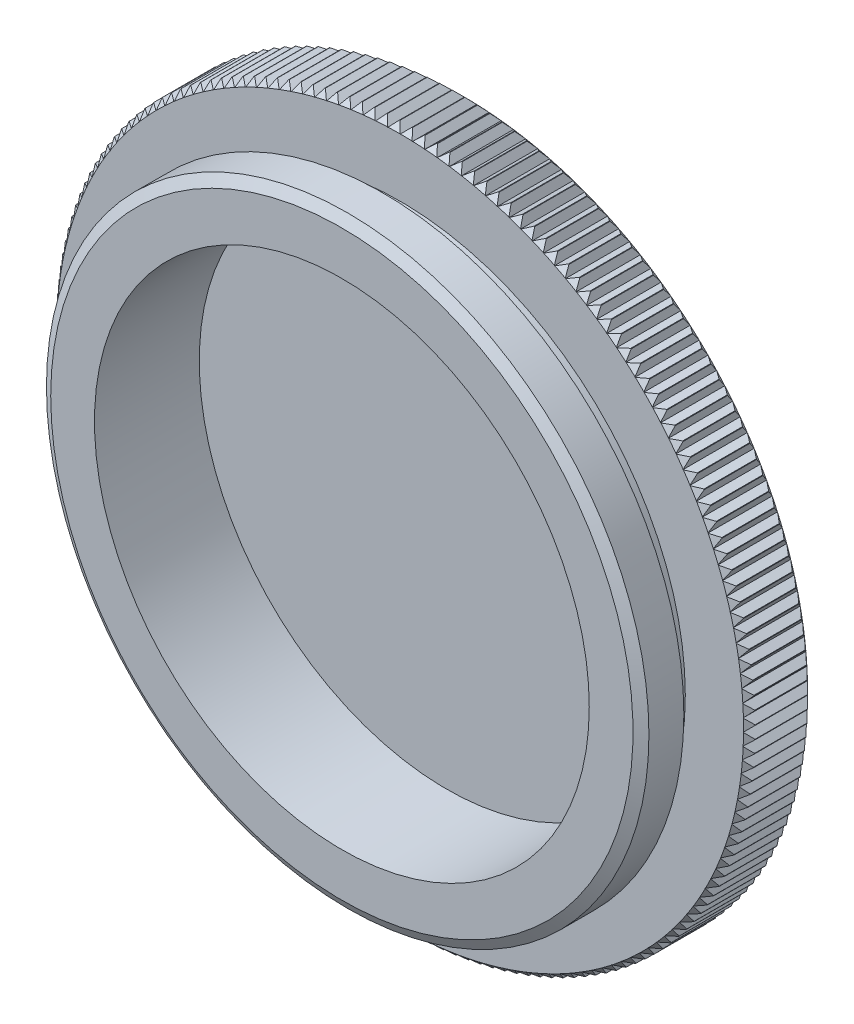
SolidWorks part; units mm, degrees
material "Anodized Aluminum"
ref_plane "Front Plane" through (0, 0, 0) normal (0, 0, 1) x (1, 0, 0)
ref_plane "Top Plane" through (0, 0, 0) normal (0, 1, 0) x (1, 0, 0)
ref_plane "Right Plane" through (0, 0, 0) normal (1, 0, 0) x (0, 0, -1)
sketch "Sketch1" plane through (0, 0, 0) normal (1, 0, 0) x (0, 0, -1)
  line L0 (0, 0) -> (1.3938, 0) construction
  line L1 (1.3938, 0) -> (1.3938, 15.24)
  line L2 (-3.9402, 0) -> (-3.9402, 13.1445)
  line L3 (1.3938, 15.24) -> (-1.4002, 15.24)
  line L4 (-1.4002, 15.24) -> (-1.4002, 12.446)
  line L5 (-1.4002, 12.446) -> (-2.1622, 12.446)
  line L6 (-2.1622, 12.446) -> (-2.1622, 13.1445)
  line L7 (-2.1622, 13.1445) -> (-3.9402, 13.1445)
  line L8 (-3.9402, 0) -> (1.3938, 0)
  dimension "D1" = 15.24
  dimension "D2" = 5.334
  dimension "D3" = 2.54
  dimension "D4" = 0.762
  dimension "D5" = 13.1445
  dimension "D6" = 12.446
revolve "Revolve1" add sketch "Sketch1" angle 360 about L0
sketch "Sketch2" plane through (0, 0, 3.9402) normal (0, 0, 1) x (1, 0, 0)
  circle A0 centre (0, 0) radius 10.795
extrude "Cut-Extrude1" cut sketch "Sketch2" against normal blind 4.572
chamfer "Chamfer1" distance 0.254 angle 60 1 edges at (13.1445, 0, 3.9402) first distance on face at (13.1445, 0, 3.9402)
chamfer "Chamfer2" distance 0.254 angle 45 2 edges at (15.24, 0, -1.3938) (15.24, 0, 1.4002)
sketch "Sketch3" plane through (0, 0, -1.3938) normal (0, 0, -1) x (-1, 0, 0)
  line L0 (0, 0) -> (0, 15.24) construction
  line L1 (0, 14.9754) -> (0.2623, 15.2377)
  line L2 (0, 14.9754) -> (-0.2623, 15.2377)
  line L3 (-0.2623, 15.2377) -> (-0.2623, 15.3523)
  line L4 (-0.2623, 15.3523) -> (0.2623, 15.3523)
  line L5 (0.2623, 15.3523) -> (0.2623, 15.2377)
  circle A0 centre (0, 0) radius 15.24 construction
  point P4 (0, 14.9754)
  dimension "D1" = 0.2646
extrude "Cut-Extrude2" cut sketch "Sketch3" against normal up to next
pattern_circular "CirPattern2" count 175 over 360 about axis through (0, 0, 0) along (0, 0, 1) of "Cut-Extrude2"
ref_plane "Plane1" through (0, 0, -1.3938) normal (0, 0, -1) x (-1, 0, 0)
sketch "Sketch6" plane through (0, 0, -1.3938) normal (0, 0, -1) x (-1, 0, 0)
  arc A0 (-11.43, 0) -> (11.43, 0) centre (0, 0) ccw construction
  text T0 "SM1CP2" font "Verdana" height 2.286
  dimension "D1" = 22.86
extrude "Cut-Extrude3" cut sketch "Sketch6" against normal blind 0.0254
sketch "Sketch7" plane through (0, 0, -1.3938) normal (0, 0, -1) x (-1, 0, 0)
  line B0 (-4.1249, 10.6598) -> (-4.5024, 11.6352)
  line B1 (-5.2654, 11.3104) -> (-4.8214, 10.3633)
  line B2 (-5.3362, 10.1079) -> (-6.2566, 11.8506)
  line B3 (-6.8728, 11.5042) -> (-5.856, 9.8159)
  line B4 (-6.342, 9.5092) -> (-7.4378, 11.1472)
  line B5 (-8.0648, 10.7024) -> (-8.4074, 11.1569)
  line B6 (-5.8997, 12.6631) -> (-5.507, 11.8256)
  line B7 (-4.7079, 12.1659) -> (-5.0417, 13.0285)
  line B8 (-4.3872, 13.2632) -> (-3.5838, 10.8536)
  line B9 (4.6468, 11.7023) -> (4.4107, 11.1076)
  line B10 (4.698, 11.5533) -> (4.5444, 11.1713)
  line B11 (4.7448, 11.9491) -> (4.9496, 12.4651)
  line B12 (5.0131, 12.3083) -> (4.8923, 12.0115)
  line B13 (3.2648, 12.8314) -> (2.7647, 12.0086)
  line B14 (3.2122, 11.3589) -> (3.2312, 10.9638)
  line B15 (2.4674, 11.1605) -> (2.679, 11.4964)
  line B16 (-0.9686, 12.317) -> (-0.8948, 11.3949)
  line B17 (-1.4664, 11.3355) -> (-1.8001, 13.8535)
  line B18 (0.0885, 12.6179) -> (0.0884, 12.6108)
  line B19 (0.5538, 13.959) -> (0.4636, 11.5394)
  line B20 (1.2791, 12.0928) -> (1.4625, 13.8932)
  line B21 (4.4933, 13.2277) -> (3.9865, 11.729)
  line B22 (-1.0554, 13.401) -> (-1.0097, 12.8302)
  line B23 (6.2847, 10.7641) -> (6.3602, 10.6829)
  line B24 (3.8677, 11.0498) -> (4.5698, 13.0682)
  line B25 (1.3159, 13.7815) -> (1.1514, 12.0153)
  line B26 (0.5821, 11.5372) -> (0.6959, 13.8266)
  line B27 (2.653, 11.6399) -> (2.419, 11.2957)
  line B28 (3.3378, 11.0558) -> (3.3017, 11.4727)
  spline B29 degree 3 poles (-3.5838, 10.8536) (-3.7657, 10.7936) (-3.9462, 10.7289) (-4.1249, 10.6598) knots 0 0 0 0 1 1 1 1
  spline B30 degree 3 poles (-4.5024, 11.6352) (-4.7603, 11.5354) (-5.0148, 11.427) (-5.2654, 11.3104) knots 0 0 0 0 1 1 1 1
  spline B31 degree 3 poles (-4.8214, 10.3633) (-4.9951, 10.2825) (-5.1668, 10.1974) (-5.3362, 10.1079) knots 0 0 0 0 1 1 1 1
  spline B32 degree 3 poles (-6.2566, 11.8506) (-6.465, 11.7405) (-6.6706, 11.6252) (-6.8728, 11.5042) knots 0 0 0 0 1 1 1 1
  spline B33 degree 3 poles (-5.856, 9.8159) (-6.0205, 9.7178) (-6.1826, 9.6155) (-6.342, 9.5092) knots 0 0 0 0 1 1 1 1
  spline B34 degree 3 poles (-7.4378, 11.1472) (-7.6509, 11.0049) (-7.8601, 10.8566) (-8.0648, 10.7024) knots 0 0 0 0 1 1 1 1
  spline B35 degree 3 poles (-8.4074, 11.1569) (-7.6272, 11.7448) (-6.7852, 12.2506) (-5.8997, 12.6631) knots 0 0 0 0 1 1 1 1
  spline B36 degree 3 poles (-5.507, 11.8256) (-5.2445, 11.9478) (-4.9779, 12.0613) (-4.7079, 12.1659) knots 0 0 0 0 1 1 1 1
  spline B37 degree 3 poles (-5.0417, 13.0285) (-4.8256, 13.1122) (-4.6073, 13.1905) (-4.3872, 13.2632) knots 0 0 0 0 1 1 1 1
  spline B38 degree 3 poles (4.9024, 10.8995) (4.74, 10.9725) (4.5761, 11.042) (4.4107, 11.1076) knots 0 0 0 0 1 1 1 1
  spline B39 degree 3 poles (4.6468, 11.7023) (4.8208, 11.6333) (4.9931, 11.5601) (5.1639, 11.4835) knots 0 0 0 0 1 1 1 1
  spline B40 degree 3 poles (5.1639, 11.4835) (5.2254, 11.4541) (5.2834, 11.3988) (5.3429, 11.2954) (5.34, 11.1934) (5.314, 11.1115) (5.2935, 11.0682) knots 0 0 0 0 0.411099 0.479762 0.711282 1 1 1 1
  spline B41 degree 3 poles (5.2935, 11.0682) (5.2717, 11.0223) (5.2312, 10.9501) (5.0972, 10.8587) (4.9753, 10.8657) (4.9024, 10.8995) knots 0 0 0 0 0.319617 0.495258 1 1 1 1
  spline B42 degree 3 poles (5.0844, 11.3885) (4.9566, 11.4457) (4.8278, 11.5007) (4.698, 11.5533) knots 0 0 0 0 1 1 1 1
  spline B43 degree 3 poles (4.5444, 11.1713) (4.6698, 11.1204) (4.7942, 11.0673) (4.9177, 11.0121) knots 0 0 0 0 1 1 1 1
  spline B44 degree 3 poles (4.9177, 11.0121) (4.976, 10.9857) (5.1032, 10.969) (5.1781, 11.0661) (5.1979, 11.1087) knots 0 0 0 0 0.577338 1 1 1 1
  spline B45 degree 3 poles (5.1979, 11.1087) (5.2177, 11.1514) (5.2561, 11.2756) (5.1464, 11.361) (5.0844, 11.3885) knots 0 0 0 0 0.409296 1 1 1 1
  spline B46 degree 3 poles (5.2203, 11.7491) (5.0631, 11.8187) (4.9046, 11.8857) (4.7448, 11.9491) knots 0 0 0 0 1 1 1 1
  spline B47 degree 3 poles (4.9496, 12.4651) (5.1162, 12.399) (5.2812, 12.3292) (5.4451, 12.2568) knots 0 0 0 0 1 1 1 1
  spline B48 degree 3 poles (5.4451, 12.2568) (5.4889, 12.2387) (5.5405, 12.1922) (5.5899, 12.1283) (5.6228, 12.0782) (5.6134, 12.0284) (5.6253, 11.9574) (5.6006, 11.9154) (5.5864, 11.8847) knots 0 0 0 0 0.311907 0.462819 0.538361 0.701729 0.776275 1 1 1 1
  spline B49 degree 3 poles (5.3534, 12.1641) (5.2407, 12.2138) (5.1272, 12.2618) (5.0131, 12.3083) knots 0 0 0 0 1 1 1 1
  spline B50 degree 3 poles (4.8923, 12.0115) (5.0038, 11.9661) (5.1148, 11.9191) (5.225, 11.8705) knots 0 0 0 0 1 1 1 1
  spline B51 degree 3 poles (5.225, 11.8705) (5.2726, 11.8521) (5.3751, 11.8195) (5.4463, 11.8996) (5.4636, 11.9378) knots 0 0 0 0 0.550069 1 1 1 1
  spline B52 degree 3 poles (5.4636, 11.9378) (5.4809, 11.9759) (5.4971, 12.0387) (5.4335, 12.1132) (5.3904, 12.1451) (5.3534, 12.1641) knots 0 0 0 0 0.435825 0.56515 1 1 1 1
  spline B53 degree 3 poles (5.5864, 11.8847) (5.5762, 11.8603) (5.5641, 11.8222) (5.5183, 11.8007) (5.4893, 11.7604) (5.4278, 11.7392) (5.3326, 11.7239) (5.2619, 11.7293) (5.2203, 11.7491) knots 0 0 0 0 0.17844 0.249355 0.331784 0.514655 0.684635 1 1 1 1
  spline B54 degree 3 poles (3.2648, 12.8314) (3.2935, 12.8241) (3.3221, 12.8167) (3.3506, 12.8092) knots 0 0 0 0 1 1 1 1
  spline B55 degree 3 poles (3.3506, 12.8092) (3.3446, 12.7931) (3.3613, 12.7731) (3.3541, 12.6984) (3.3486, 12.6254) (3.3771, 12.5185) (3.3591, 12.444) (3.3828, 12.3436) (3.3663, 12.2696) (3.3869, 12.1689) (3.3722, 12.0954) (3.3921, 11.9803) (3.3822, 11.9075) (3.3817, 11.8497) knots 0 0 0 0 0.047149 0.070715 0.22885 0.274598 0.410948 0.456594 0.592739 0.638286 0.774235 0.819687 1 1 1 1
  spline B56 degree 3 poles (3.3817, 11.8497) (3.1775, 11.908) (2.9718, 11.9611) (2.7647, 12.0086) knots 0 0 0 0 1 1 1 1
  spline B57 degree 3 poles (3.2393, 12.5884) (3.2172, 12.5499) (3.195, 12.4936) (3.1236, 12.4164) (3.1006, 12.3426) (3.0272, 12.2577) (2.9894, 12.1762) (2.9462, 12.1159) (2.94, 12.0928) knots 0 0 0 0 0.229779 0.307153 0.537937 0.615146 0.88288 1 1 1 1
  spline B58 degree 3 poles (2.94, 12.0928) (3.0474, 12.0668) (3.1544, 12.0392) (3.261, 12.0102) knots 0 0 0 0 1 1 1 1
  spline B59 degree 3 poles (3.261, 12.0102) (3.2608, 12.0693) (3.271, 12.1438) (3.2475, 12.2609) (3.263, 12.3363) (3.2393, 12.4384) (3.2432, 12.5134) (3.2477, 12.574) (3.2393, 12.5884) knots 0 0 0 0 0.305373 0.382414 0.612761 0.689965 0.919377 1 1 1 1
  spline B60 degree 3 poles (4.7666, 10.3886) (4.7924, 10.3782) (4.8433, 10.3576) (4.9223, 10.3356) (5.002, 10.3208) (5.0825, 10.3139) (5.2033, 10.3146) (5.3666, 10.3443) (5.4798, 10.4196) (5.5365, 10.4573) knots 0 0 0 0 0.102661 0.203283 0.302721 0.401862 0.5016 0.750321 1 1 1 1
  spline B61 degree 3 poles (3.2312, 10.9638) (3.7559, 10.8091) (4.2695, 10.6168) (4.7666, 10.3886) knots 0 0 0 0 1 1 1 1
  spline B62 degree 3 poles (2.679, 11.4964) (2.8578, 11.4547) (3.0356, 11.4089) (3.2122, 11.3589) knots 0 0 0 0 1 1 1 1
  spline B63 degree 3 poles (2.4674, 11.1605) (1.634, 11.3448) (0.7798, 11.4353) (-0.0737, 11.4298) knots 0 0 0 0 1 1 1 1
  spline B64 degree 3 poles (-0.0737, 11.4298) (-0.1345, 11.5555) (-0.1345, 11.6973) (-0.1447, 11.8347) knots 0 0 0 0 1 1 1 1
  spline B65 degree 3 poles (-0.1447, 11.8347) (-0.159, 11.9491) (-0.161, 12.2006) (-0.3731, 12.3657) (-0.4977, 12.345) knots 0 0 0 0 0.51231 1 1 1 1
  spline B66 degree 3 poles (-0.4977, 12.345) (-0.6548, 12.3386) (-0.8118, 12.3293) (-0.9686, 12.317) knots 0 0 0 0 1 1 1 1
  spline B67 degree 3 poles (-0.8948, 11.3949) (-1.0858, 11.3799) (-1.2764, 11.3601) (-1.4664, 11.3355) knots 0 0 0 0 1 1 1 1
  spline B68 degree 3 poles (-1.8001, 13.8535) (-1.3448, 13.9127) (-0.8867, 13.9494) (-0.4278, 13.9634) knots 0 0 0 0 1 1 1 1
  spline B69 degree 3 poles (-0.4278, 13.9634) (-0.2571, 13.9656) (0.0217, 13.9243) (0.4155, 13.6966) (0.4947, 13.4099) (0.4938, 13.2458) knots 0 0 0 0 0.389262 0.628458 1 1 1 1
  spline B70 degree 3 poles (0.4938, 13.2458) (0.4783, 13.1445) (0.4438, 12.879) (0.237, 12.6779) (0.0885, 12.6179) knots 0 0 0 0 0.392978 1 1 1 1
  spline B71 degree 3 poles (0.0884, 12.6108) (0.217, 12.5819) (0.3877, 12.3746) (0.414, 12.1203) (0.4207, 11.9954) knots 0 0 0 0 0.493911 1 1 1 1
  spline B72 degree 3 poles (0.4207, 11.9954) (0.4275, 11.8427) (0.4346, 11.6895) (0.4636, 11.5394) knots 0 0 0 0 1 1 1 1
  spline B73 degree 3 poles (1.4625, 13.8932) (1.3631, 13.9031) (1.163, 13.923) (0.86, 13.9449) (0.6563, 13.9543) (0.5538, 13.959) knots 0 0 0 0 0.328821 0.6621 1 1 1 1
  spline B74 degree 3 poles (2.0836, 11.9804) (1.9497, 12.0025) (1.6825, 12.0467) (1.4133, 12.0774) (1.2791, 12.0928) knots 0 0 0 0 0.501119 1 1 1 1
  spline B75 degree 3 poles (3.0994, 13.6218) (3.0977, 13.6176) (3.0934, 13.6072) (3.0803, 13.5915) (3.0634, 13.5764) (3.0463, 13.5527) (3.0233, 13.5132) (2.9968, 13.4666) (2.966, 13.4276) (2.9396, 13.397) (2.9128, 13.3551) (2.8747, 13.2953) (2.8056, 13.1794) (2.7058, 13.0157) (2.5718, 12.8147) (2.4383, 12.6132) (2.3132, 12.4062) (2.1939, 12.1958) (2.1204, 12.0522) (2.0836, 11.9804) knots 0 0 0 0 0.007038 0.017393 0.031338 0.042113 0.062535 0.102492 0.12493 0.139585 0.16523 0.201946 0.249759 0.374586 0.499414 0.624627 0.749707 0.874786 1 1 1 1
  spline B76 degree 3 poles (3.9049, 13.4131) (3.7733, 13.4504) (3.5064, 13.5259) (3.2363, 13.5896) (3.0994, 13.6218) knots 0 0 0 0 0.493027 1 1 1 1
  spline B77 degree 3 poles (3.9865, 11.729) (3.9877, 11.7427) (3.9909, 11.7798) (3.9888, 11.8504) (3.9846, 11.9577) (3.9797, 12.0612) (3.9749, 12.155) (3.9784, 12.2215) (3.9781, 12.2919) (3.9769, 12.3623) (3.974, 12.4326) (3.9698, 12.5029) (3.9568, 12.6511) (3.9369, 12.8691) (3.917, 13.1492) (3.9088, 13.3279) (3.9049, 13.4131) knots 0 0 0 0 0.024453 0.0662 0.125345 0.21551 0.25042 0.292177 0.333897 0.375597 0.417298 0.459017 0.500775 0.681887 0.848277 1 1 1 1
  spline B78 degree 3 poles (5.6019, 12.7976) (5.5106, 12.837) (5.3282, 12.9156) (5.0517, 13.0258) (4.7738, 13.1307) (4.5868, 13.1954) (4.4933, 13.2277) knots 0 0 0 0 0.250742 0.500912 0.750626 1 1 1 1
  spline B79 degree 3 poles (6.3236, 11.9399) (6.3249, 11.9464) (6.3276, 11.9608) (6.3248, 11.9838) (6.3212, 12.0058) (6.32, 12.0381) (6.3226, 12.0728) (6.3182, 12.107) (6.3139, 12.132) (6.3139, 12.1541) (6.3126, 12.1774) (6.3029, 12.2111) (6.289, 12.2438) (6.2751, 12.2817) (6.2569, 12.3065) (6.2391, 12.3341) (6.2206, 12.3601) (6.2022, 12.385) (6.1837, 12.4086) (6.1652, 12.431) (6.1466, 12.4522) (6.1279, 12.4721) (6.1092, 12.4908) (6.0905, 12.5083) (6.0717, 12.5246) (6.0176, 12.5672) (5.9193, 12.6334) (5.7687, 12.7198) (5.6592, 12.7709) (5.6019, 12.7976) knots 0 0 0 0 0.016471 0.035894 0.056952 0.0716 0.115848 0.142773 0.156791 0.178573 0.197456 0.21431 0.265096 0.28561 0.313594 0.34075 0.367092 0.392634 0.417392 0.441385 0.464631 0.487152 0.508972 0.530116 0.550612 0.570493 0.700702 0.843598 1 1 1 1
  spline B80 degree 3 poles (7.4404, 11.8523) (7.4094, 11.8711) (7.3464, 11.9095) (7.2436, 11.9569) (7.1332, 11.9983) (7.0146, 12.0323) (6.8961, 12.0596) (6.7784, 12.0736) (6.6645, 12.0671) (6.5501, 12.0428) (6.4348, 12.001) (6.3615, 11.9607) (6.3236, 11.9399) knots 0 0 0 0 0.091885 0.187178 0.286565 0.390651 0.499963 0.594891 0.690115 0.787978 0.890647 1 1 1 1
  spline B81 degree 3 poles (7.787, 10.4503) (7.8312, 10.5117) (7.9066, 10.6167) (7.9827, 10.7656) (8.0146, 10.884) (8.0299, 10.9799) (8.0248, 11.0721) (8.0081, 11.157) (7.9906, 11.2349) (7.9718, 11.2966) (7.9448, 11.3515) (7.9122, 11.3998) (7.8829, 11.4472) (7.8605, 11.482) (7.8459, 11.5048) (7.8313, 11.5259) (7.8086, 11.549) (7.7764, 11.5832) (7.7358, 11.623) (7.674, 11.6839) (7.5763, 11.7641) (7.4892, 11.8206) (7.4404, 11.8523) knots 0 0 0 0 0.13412 0.229083 0.294321 0.350938 0.400339 0.457058 0.50422 0.542049 0.570987 0.612367 0.645287 0.669748 0.685752 0.693305 0.715245 0.74299 0.776563 0.815975 0.896876 1 1 1 1
  spline B82 degree 3 poles (7.2231, 10.8447) (7.3184, 10.7808) (7.5089, 10.6529) (7.6943, 10.5178) (7.787, 10.4503) knots 0 0 0 0 0.500312 1 1 1 1
  spline B83 degree 3 poles (7.2331, 10.8326) (7.2298, 10.8367) (7.2265, 10.8407) (7.2231, 10.8447) knots 0 0 0 0 1 1 1 1
  spline B84 degree 3 poles (7.3576, 9.7638) (7.3693, 9.7859) (7.3928, 9.8299) (7.4301, 9.8779) (7.4576, 9.9224) (7.478, 9.9681) (7.5057, 10.0303) (7.5291, 10.1121) (7.5347, 10.2119) (7.5289, 10.3194) (7.4982, 10.4354) (7.4369, 10.5567) (7.3478, 10.6925) (7.2734, 10.7834) (7.2331, 10.8326) knots 0 0 0 0 0.062599 0.125198 0.152224 0.193909 0.250453 0.323478 0.406022 0.500446 0.59273 0.705084 0.840308 1 1 1 1
  spline B85 degree 3 poles (6.4349, 9.4465) (6.4684, 9.4402) (6.5352, 9.4275) (6.6371, 9.4218) (6.7395, 9.4262) (6.8422, 9.4417) (6.9518, 9.4687) (7.0654, 9.513) (7.1748, 9.5823) (7.2736, 9.6659) (7.3296, 9.7312) (7.3576, 9.7638) knots 0 0 0 0 0.099186 0.197672 0.296543 0.39687 0.49968 0.624694 0.749903 0.874952 1 1 1 1
  spline B86 degree 3 poles (5.7292, 9.8904) (5.9101, 9.6561) (6.1454, 9.5082) (6.4349, 9.4465) knots 0 0 0 0 1 1 1 1
  spline B87 degree 3 poles (5.5365, 10.4573) (5.5339, 10.4328) (5.5287, 10.3833) (5.5334, 10.3075) (5.5472, 10.2305) (5.5764, 10.1329) (5.6327, 10.0145) (5.6959, 9.9332) (5.7292, 9.8904) knots 0 0 0 0 0.119789 0.241753 0.367851 0.499859 0.736813 1 1 1 1
  spline B88 degree 3 poles (-0.5208, 13.4324) (-0.6992, 13.4256) (-0.8774, 13.4151) (-1.0554, 13.401) knots 0 0 0 0 1 1 1 1
  spline B89 degree 3 poles (-1.0097, 12.8302) (-0.8288, 12.8444) (-0.6477, 12.8548) (-0.4664, 12.8614) knots 0 0 0 0 1 1 1 1
  spline B90 degree 3 poles (-0.4664, 12.8614) (-0.3899, 12.8628) (-0.2132, 12.9119) (-0.1673, 13.0904) (-0.1742, 13.1674) knots 0 0 0 0 0.500411 1 1 1 1
  spline B91 degree 3 poles (-0.1742, 13.1674) (-0.1616, 13.2542) (-0.2652, 13.4065) (-0.4385, 13.4357) (-0.5208, 13.4324) knots 0 0 0 0 0.491347 1 1 1 1
  spline B92 degree 3 poles (5.8871, 10.9508) (5.8923, 10.9616) (5.9033, 10.9841) (5.9154, 11.0213) (5.927, 11.0612) (5.9296, 11.1145) (5.9306, 11.1634) (5.925, 11.2077) (5.9148, 11.2454) (5.904, 11.293) (5.8872, 11.3494) (5.8694, 11.3843) (5.8605, 11.4018) knots 0 0 0 0 0.076764 0.159925 0.250157 0.340866 0.500116 0.562467 0.625104 0.749708 0.874854 1 1 1 1
  spline B93 degree 3 poles (6.3602, 10.6829) (6.2823, 10.7287) (6.1261, 10.8206) (5.9669, 10.9073) (5.8871, 10.9508) knots 0 0 0 0 0.498243 1 1 1 1
  spline B94 degree 3 poles (6.0754, 11.5214) (6.0725, 11.5155) (6.0638, 11.4977) (6.0534, 11.4591) (6.0383, 11.4066) (6.0256, 11.3479) (6.0287, 11.2745) (6.042, 11.2124) (6.0501, 11.1513) (6.0628, 11.1066) (6.0905, 11.0466) (6.1277, 10.9787) (6.1719, 10.9008) (6.2217, 10.8282) (6.2637, 10.7855) (6.2847, 10.7641) knots 0 0 0 0 0.023724 0.071176 0.142608 0.220527 0.285416 0.404691 0.448293 0.506749 0.570883 0.684931 0.785145 0.892573 1 1 1 1
  spline B95 degree 3 poles (5.8605, 11.4018) (5.8673, 11.4055) (5.8863, 11.4159) (5.9256, 11.4301) (5.9766, 11.4454) (6.033, 11.4729) (6.0607, 11.5046) (6.0754, 11.5214) knots 0 0 0 0 0.093097 0.259539 0.500072 0.734113 1 1 1 1
  spline B96 degree 3 poles (6.7557, 11.3819) (6.7512, 11.3709) (6.742, 11.3484) (6.7407, 11.31) (6.7483, 11.2688) (6.7657, 11.2245) (6.7921, 11.1737) (6.8521, 11.1051) (6.9432, 11.0026) (7.0499, 10.8855) (7.1254, 10.8069) (7.1561, 10.775) knots 0 0 0 0 0.046526 0.095262 0.149376 0.211215 0.282364 0.374597 0.569403 0.825217 1 1 1 1
  spline B97 degree 3 poles (7.1057, 11.3975) (7.0814, 11.4115) (7.0366, 11.4373) (6.9677, 11.461) (6.9043, 11.4682) (6.8463, 11.457) (6.7947, 11.4278) (6.7691, 11.3977) (6.7557, 11.3819) knots 0 0 0 0 0.214187 0.396682 0.554535 0.698461 0.842323 1 1 1 1
  spline B98 degree 3 poles (7.2735, 10.9622) (7.2822, 10.9779) (7.2944, 10.9999) (7.3123, 11.0279) (7.3139, 11.0611) (7.3213, 11.0958) (7.3209, 11.137) (7.3107, 11.1738) (7.2918, 11.221) (7.255, 11.2765) (7.202, 11.3262) (7.1512, 11.3679) (7.1194, 11.3886) (7.1057, 11.3975) knots 0 0 0 0 0.101751 0.142492 0.183691 0.28536 0.343561 0.414188 0.499542 0.62972 0.785817 0.907651 1 1 1 1
  spline B99 degree 3 poles (7.7592, 10.624) (7.6788, 10.682) (7.5188, 10.7973) (7.355, 10.9074) (7.2735, 10.9622) knots 0 0 0 0 0.502286 1 1 1 1
  spline B100 degree 3 poles (7.393, 11.7615) (7.4171, 11.7461) (7.4666, 11.7145) (7.5377, 11.6581) (7.6388, 11.5666) (7.7528, 11.4424) (7.8427, 11.2803) (7.8819, 11.1311) (7.8937, 10.9957) (7.8767, 10.8648) (7.8331, 10.7381) (7.7843, 10.6627) (7.7592, 10.624) knots 0 0 0 0 0.063363 0.130214 0.20092 0.365868 0.501764 0.607214 0.705805 0.801365 0.898081 1 1 1 1
  spline B101 degree 3 poles (6.219, 11.6403) (6.2341, 11.6666) (6.2633, 11.7177) (6.3172, 11.7852) (6.3767, 11.8422) (6.4424, 11.8882) (6.5143, 11.9233) (6.5921, 11.9473) (6.6758, 11.9605) (6.8078, 11.963) (6.9846, 11.9404) (7.1993, 11.8747) (7.328, 11.7996) (7.393, 11.7615) knots 0 0 0 0 0.067952 0.131849 0.19281 0.252121 0.311174 0.371382 0.434078 0.500445 0.666908 0.831534 1 1 1 1
  spline B102 degree 3 poles (6.4597, 10.7456) (6.4339, 10.7785) (6.3823, 10.8443) (6.3086, 10.927) (6.2486, 11.0031) (6.2082, 11.0771) (6.1718, 11.1707) (6.1455, 11.2801) (6.1342, 11.4003) (6.16, 11.5228) (6.1977, 11.5978) (6.219, 11.6403) knots 0 0 0 0 0.124967 0.249933 0.331136 0.414204 0.50069 0.631021 0.749751 0.858448 1 1 1 1
  spline B103 degree 3 poles (6.8042, 10.1322) (6.811, 10.1455) (6.8246, 10.1719) (6.8323, 10.2166) (6.8295, 10.2633) (6.8158, 10.3122) (6.7917, 10.3632) (6.7574, 10.4166) (6.7026, 10.4835) (6.6308, 10.563) (6.5465, 10.6554) (6.4886, 10.7156) (6.4597, 10.7456) knots 0 0 0 0 0.059548 0.118106 0.179115 0.245637 0.320055 0.404084 0.498918 0.665955 0.832963 1 1 1 1
  spline B104 degree 3 poles (6.3968, 10.1187) (6.4225, 10.1039) (6.4708, 10.0761) (6.5458, 10.0493) (6.6167, 10.0384) (6.686, 10.043) (6.7543, 10.0726) (6.7869, 10.1115) (6.8042, 10.1322) knots 0 0 0 0 0.195858 0.368708 0.523684 0.66784 0.82352 1 1 1 1
  spline B105 degree 3 poles (6.2396, 10.6306) (6.2247, 10.6002) (6.1951, 10.5398) (6.1763, 10.439) (6.1885, 10.343) (6.2317, 10.2573) (6.3026, 10.1835) (6.3633, 10.1417) (6.3968, 10.1187) knots 0 0 0 0 0.166863 0.331632 0.499604 0.63575 0.799575 1 1 1 1
  spline B106 degree 3 poles (5.7741, 10.8905) (5.8517, 10.8488) (6.0083, 10.7647) (6.1621, 10.6755) (6.2396, 10.6306) knots 0 0 0 0 0.495698 1 1 1 1
  spline B107 degree 3 poles (5.6603, 11.4916) (5.6734, 11.4811) (5.6997, 11.46) (5.7329, 11.4209) (5.7615, 11.3765) (5.7851, 11.3263) (5.8036, 11.2704) (5.8244, 11.1783) (5.8309, 11.0454) (5.7931, 10.9424) (5.7741, 10.8905) knots 0 0 0 0 0.076425 0.153744 0.233603 0.317501 0.40673 0.502368 0.749365 1 1 1 1
  spline B108 degree 3 poles (6.1319, 11.7694) (6.1196, 11.7474) (6.0954, 11.7043) (6.0491, 11.6477) (5.9966, 11.5997) (5.9249, 11.554) (5.8404, 11.5155) (5.7466, 11.4872) (5.6875, 11.4902) (5.6603, 11.4916) knots 0 0 0 0 0.131007 0.255955 0.377569 0.498799 0.694941 0.859492 1 1 1 1
  spline B109 degree 3 poles (5.6174, 12.6533) (5.6569, 12.6357) (5.7339, 12.6014) (5.8409, 12.5404) (5.9374, 12.4739) (6.0229, 12.4012) (6.0978, 12.323) (6.1582, 12.2401) (6.1852, 12.1538) (6.193, 12.0816) (6.1994, 12.026) (6.2022, 11.9847) (6.1999, 11.947) (6.1888, 11.9085) (6.1743, 11.863) (6.1552, 11.8163) (6.1398, 11.7853) (6.1319, 11.7694) knots 0 0 0 0 0.110356 0.214747 0.313935 0.408806 0.500373 0.590073 0.667314 0.72763 0.775253 0.810273 0.832932 0.871374 0.911894 0.954707 1 1 1 1
  spline B110 degree 3 poles (4.5698, 13.0682) (4.657, 13.0372) (4.8322, 12.9749) (5.0938, 12.8739) (5.3561, 12.7673) (5.53, 12.6914) (5.6174, 12.6533) knots 0 0 0 0 0.246325 0.49503 0.746221 1 1 1 1
  spline B111 degree 3 poles (3.7628, 13.323) (3.7636, 13.3001) (3.766, 13.2379) (3.7758, 13.1207) (3.79, 12.9549) (3.8106, 12.7437) (3.8304, 12.5247) (3.8456, 12.3356) (3.8478, 12.1811) (3.8543, 11.9498) (3.8634, 11.665) (3.8707, 11.3349) (3.8687, 11.1448) (3.8677, 11.0498) knots 0 0 0 0 0.030231 0.081882 0.154973 0.249511 0.361461 0.444708 0.499329 0.565029 0.749569 0.874784 1 1 1 1
  spline B112 degree 3 poles (3.1427, 13.4827) (3.2445, 13.4584) (3.4521, 13.4088) (3.6579, 13.3519) (3.7628, 13.323) knots 0 0 0 0 0.490381 1 1 1 1
  spline B113 degree 3 poles (2.146, 11.8781) (2.1579, 11.8963) (2.1932, 11.9499) (2.2577, 12.0597) (2.3537, 12.2228) (2.4795, 12.4402) (2.6111, 12.6724) (2.745, 12.8975) (2.8791, 13.0918) (3.0152, 13.2844) (3.1002, 13.4166) (3.1427, 13.4827) knots 0 0 0 0 0.034581 0.101921 0.202047 0.334967 0.500683 0.625632 0.75058 0.87529 1 1 1 1
  spline B114 degree 3 poles (1.1514, 12.0153) (1.2625, 12.0038) (1.4844, 11.9807) (1.8161, 11.9349) (2.036, 11.897) (2.146, 11.8781) knots 0 0 0 0 0.333489 0.666735 1 1 1 1
  spline B115 degree 3 poles (0.6959, 13.8266) (0.7985, 13.8208) (1.0054, 13.8091) (1.2118, 13.7907) (1.3159, 13.7815) knots 0 0 0 0 0.495787 1 1 1 1
  spline B116 degree 3 poles (2.419, 11.2957) (2.3179, 11.3166) (2.116, 11.3582) (1.8113, 11.4103) (1.5056, 11.4548) (1.1988, 11.4908) (0.8909, 11.5192) (0.6851, 11.5312) (0.5821, 11.5372) knots 0 0 0 0 0.166863 0.333488 0.499995 0.666503 0.833131 1 1 1 1
  spline B117 degree 3 poles (3.3017, 11.4727) (3.1938, 11.503) (2.9787, 11.5632) (2.7613, 11.6144) (2.653, 11.6399) knots 0 0 0 0 0.501866 1 1 1 1
  spline B118 degree 3 poles (4.7109, 10.5442) (4.6213, 10.5834) (4.4422, 10.6619) (4.1699, 10.7709) (3.8952, 10.8733) (3.618, 10.969) (3.4312, 11.0269) (3.3378, 11.0558) knots 0 0 0 0 0.200142 0.400084 0.599955 0.799884 1 1 1 1
  spline B119 degree 3 poles (5.681, 10.7269) (5.6595, 10.7006) (5.6179, 10.6494) (5.5466, 10.5838) (5.4712, 10.5301) (5.391, 10.4887) (5.3064, 10.4596) (5.2173, 10.443) (5.1238, 10.4387) (5.0261, 10.4468) (4.9242, 10.4671) (4.8179, 10.4991) (4.7474, 10.5288) (4.7109, 10.5442) knots 0 0 0 0 0.094203 0.183135 0.268162 0.350843 0.432873 0.515983 0.601843 0.691967 0.787669 0.890047 1 1 1 1
  spline B120 degree 3 poles (6.1085, 9.7205) (6.0786, 9.7402) (6.02, 9.7788) (5.9402, 9.8444) (5.8693, 9.914) (5.8077, 9.9881) (5.7554, 10.0665) (5.6962, 10.1805) (5.6465, 10.3353) (5.633, 10.5346) (5.6648, 10.6621) (5.681, 10.7269) knots 0 0 0 0 0.091052 0.178059 0.261712 0.34279 0.422148 0.500694 0.668282 0.831248 1 1 1 1
  spline B121 degree 3 poles (7.296, 9.8717) (7.2745, 9.844) (7.2326, 9.7899) (7.1612, 9.7191) (7.0859, 9.6594) (7.006, 9.6112) (6.9216, 9.5747) (6.8328, 9.5497) (6.6689, 9.5263) (6.4092, 9.5552) (6.213, 9.663) (6.1085, 9.7205) knots 0 0 0 0 0.078883 0.153589 0.225046 0.294313 0.362551 0.430974 0.500786 0.734047 1 1 1 1
  spline B122 degree 3 poles (7.1561, 10.775) (7.1914, 10.7266) (7.2407, 10.6591) (7.3161, 10.56) (7.3685, 10.4654) (7.4197, 10.3094) (7.4279, 10.0905) (7.3408, 9.946) (7.296, 9.8717) knots 0 0 0 0 0.180087 0.251064 0.374031 0.502444 0.744262 1 1 1 1
  spline B123 degree 3 poles (6.8623, 11.3121) (6.8711, 11.3138) (6.8895, 11.3175) (6.9196, 11.3144) (6.9522, 11.3057) (6.9877, 11.2907) (7.0262, 11.2699) (7.0519, 11.2525) (7.0656, 11.2433) knots 0 0 0 0 0.120711 0.254098 0.40557 0.578849 0.776432 1 1 1 1
  spline B124 degree 3 poles (7.1172, 10.961) (7.0923, 10.9887) (7.0425, 11.0443) (6.9649, 11.1248) (6.9068, 11.1878) (6.8734, 11.2326) (6.8605, 11.2574) (6.8569, 11.2841) (6.8605, 11.3026) (6.8623, 11.3121) knots 0 0 0 0 0.249998 0.499993 0.74977 0.823907 0.874322 0.935463 1 1 1 1
  spline B125 degree 3 poles (7.1645, 11.0441) (7.1575, 11.0297) (7.1433, 11.0011) (7.1259, 10.9743) (7.1172, 10.961) knots 0 0 0 0 0.5 1 1 1 1
  spline B126 degree 3 poles (7.0656, 11.2433) (7.0865, 11.2298) (7.1243, 11.2052) (7.1643, 11.1554) (7.18, 11.0983) (7.1698, 11.0625) (7.1645, 11.0441) knots 0 0 0 0 0.304152 0.550456 0.768754 1 1 1 1
  spline B127 degree 3 poles (6.3732, 10.6699) (6.3831, 10.6581) (6.4139, 10.6213) (6.4624, 10.5681) (6.5148, 10.5069) (6.5549, 10.4529) (6.5908, 10.4019) (6.6257, 10.3551) (6.6574, 10.3096) (6.6783, 10.2667) (6.689, 10.2292) (6.6829, 10.208) (6.6802, 10.1986) knots 0 0 0 0 0.080162 0.249946 0.374932 0.499918 0.599829 0.699741 0.80444 0.886897 0.949977 1 1 1 1
  spline B128 degree 3 poles (6.3857, 10.2855) (6.372, 10.3025) (6.3467, 10.3341) (6.3173, 10.3815) (6.3003, 10.4278) (6.2923, 10.4864) (6.317, 10.5714) (6.352, 10.6327) (6.3732, 10.6699) knots 0 0 0 0 0.154481 0.285852 0.391549 0.500756 0.6976 1 1 1 1
  spline B129 degree 3 poles (6.6802, 10.1986) (6.6704, 10.1899) (6.6535, 10.1748) (6.6172, 10.1513) (6.559, 10.1464) (6.4964, 10.1789) (6.4375, 10.2266) (6.4037, 10.2649) (6.3857, 10.2855) knots 0 0 0 0 0.110527 0.191091 0.361531 0.570319 0.769912 1 1 1 1
  spline B130 degree 3 poles (6.4349, 9.4465) (6.7701, 9.3709) (7.1461, 9.4934) (7.3576, 9.7638) knots 0 0 0 0 1 1 1 1
  spline B131 degree 3 poles (5.5365, 10.4573) (5.5298, 10.4067) (5.523, 10.3547) (5.5352, 10.3049) (5.5356, 10.3036) knots 0 0 0 0 0.973937 1 1 1 1
  spline B132 degree 3 poles (5.6463, 10.0059) (5.6519, 9.9963) (5.6757, 9.9553) (5.706, 9.9186) (5.7292, 9.8904) knots 0 0 0 0 0.232817 1 1 1 1
  spline B133 degree 3 poles (-2.656, 11.6495) (-2.4657, 11.6929) (-2.2885, 11.881) (-2.2509, 12.1791) (-2.2383, 12.3309) (-2.248, 12.4535) (-2.2638, 12.4992) knots 0 0 0 0 0.562745 0.646334 0.864258 1 1 1 1
  spline B134 degree 3 poles (-2.2638, 12.4992) (-2.264, 12.5318) (-2.3099, 12.6151) (-2.3261, 12.7405) (-2.4082, 12.8663) (-2.5227, 13.0269) (-2.7392, 13.1561) (-2.9246, 13.1352) (-2.9951, 13.1192) knots 0 0 0 0 0.086884 0.256976 0.339446 0.499652 0.800415 1 1 1 1
  spline B135 degree 3 poles (-2.9951, 13.1192) (-3.0868, 13.095) (-3.265, 13.0249) (-3.3848, 12.8079) (-3.4126, 12.6371) (-3.4348, 12.4571) (-3.401, 12.3352) (-3.3762, 12.2457) knots 0 0 0 0 0.264017 0.500269 0.660568 0.74313 1 1 1 1
  spline B136 degree 3 poles (-3.3762, 12.2457) (-3.3435, 12.1275) (-3.2352, 11.8929) (-2.9751, 11.6269) (-2.74, 11.6311) (-2.656, 11.6495) knots 0 0 0 0 0.353143 0.751721 1 1 1 1
  spline B137 degree 3 poles (-2.536, 11.1451) (-2.7197, 11.1037) (-3.1303, 11.1019) (-3.5579, 11.3643) (-3.7615, 11.6491) (-3.8866, 11.8432) (-3.9525, 11.9765) (-3.9833, 12.0614) knots 0 0 0 0 0.300139 0.631146 0.76377 0.856013 1 1 1 1
  spline B138 degree 3 poles (-1.635, 12.5933) (-1.6224, 12.4748) (-1.6345, 12.2722) (-1.6616, 12.0145) (-1.759, 11.7638) (-1.964, 11.388) (-2.3033, 11.1986) (-2.536, 11.1451) knots 0 0 0 0 0.190406 0.32531 0.411645 0.618476 1 1 1 1
  spline B139 degree 3 poles (-3.9833, 12.0614) (-4.0024, 12.1241) (-4.0323, 12.2105) (-4.0367, 12.3591) (-4.0421, 12.469) (-4.053, 12.5835) (-4.035, 12.6662) (-4.0315, 12.7775) (-3.9618, 12.989) (-3.8255, 13.2054) (-3.6072, 13.3971) (-3.3975, 13.5406) (-3.2086, 13.595) (-3.1112, 13.6191) knots 0 0 0 0 0.096641 0.132884 0.21833 0.260327 0.301261 0.342195 0.423693 0.627329 0.713521 0.851739 1 1 1 1
  spline B140 degree 3 poles (-3.1112, 13.6191) (-2.98, 13.6493) (-2.7818, 13.6782) (-2.4987, 13.6428) (-2.3367, 13.5668) (-2.1516, 13.4925) (-2.0349, 13.4082) (-1.9362, 13.2729) (-1.8551, 13.1943) (-1.7961, 13.0653) (-1.7461, 12.9627) (-1.6649, 12.8043) (-1.6492, 12.6828) (-1.635, 12.5933) knots 0 0 0 0 0.196988 0.287333 0.413979 0.455898 0.578022 0.618053 0.699329 0.740692 0.824682 0.867529 1 1 1 1
sketch_block_instance "Block-Ø0.9-0.1-1"
sketch_block "Block1"
extrude "Cut-Extrude4" cut sketch "Sketch7" against normal blind 0.0254 contours B37 B7 B36 B6 B35 B5 B34 B4 B33 B3 B32 B2 B31 B1 B30 B0 B29 B8 | B140 B139 B137 B138 B136 B135 B134 B133 | B85 B130 B84 B83 B82 B81 B80 B79 B78 B21 B77 B76 B75 B74 B20 B73 B19 B72 B71 B18 B70 B69 B68 B17 B67 B16 B66 B65 B64 B63 B15 B62 B14 B61 B60 B87 B86 B127 B129 B128 B96 B122 | B53 B48 B47 B11 B46 B52 B51 B50 B12 B49 | B41 B40 B39 B9 B38 B45 B44 B43 B10 B42 | B56 B55 B54 B13 B59 B58 B57 region at (5.7853, 11.4375, -1.3938) region at (-4.9017, 11.5842, -1.3938) region at (-4.8578, 12.2028, -1.3938) region at (-3.3048, 12.8091, -1.3938) region at (-2.9734, 11.5356, -1.3938) region at (3.4164, 11.3378, -1.3938)
sketch "Sketch8" plane through (0, 0, -1.3938) normal (0, 0, -1) x (-1, 0, 0)
  circle A0 centre (0, 0) radius 11.43
  dimension "D1" = 22.86
sketch "Sketch9" plane through (0, 0, -1.3938) normal (0, 0, -1) x (-1, 0, 0)
  line L0 (0, 0) -> (0.0635, 0.0635)
  line L1 (0.0635, 0.0635) -> (0.0635, 5.1435)
  line L2 (0.0635, 5.1435) -> (-0.0635, 5.1435)
  line L3 (-0.0635, 5.1435) -> (-0.0635, 0.0635)
  line L4 (-0.0635, 0.0635) -> (0, 0)
  dimension "D1" = 90
  dimension "D2" = 0.0635
  dimension "D3" = 0.0635
  dimension "D4" = 5.08
extrude "Cut-Extrude5" cut sketch "Sketch9" against normal blind 0.0254
pattern_circular "CirPattern3" count 4 over 360 about axis through (0, 0, 3.9402) along (0, 0, 1) of "Cut-Extrude5"
